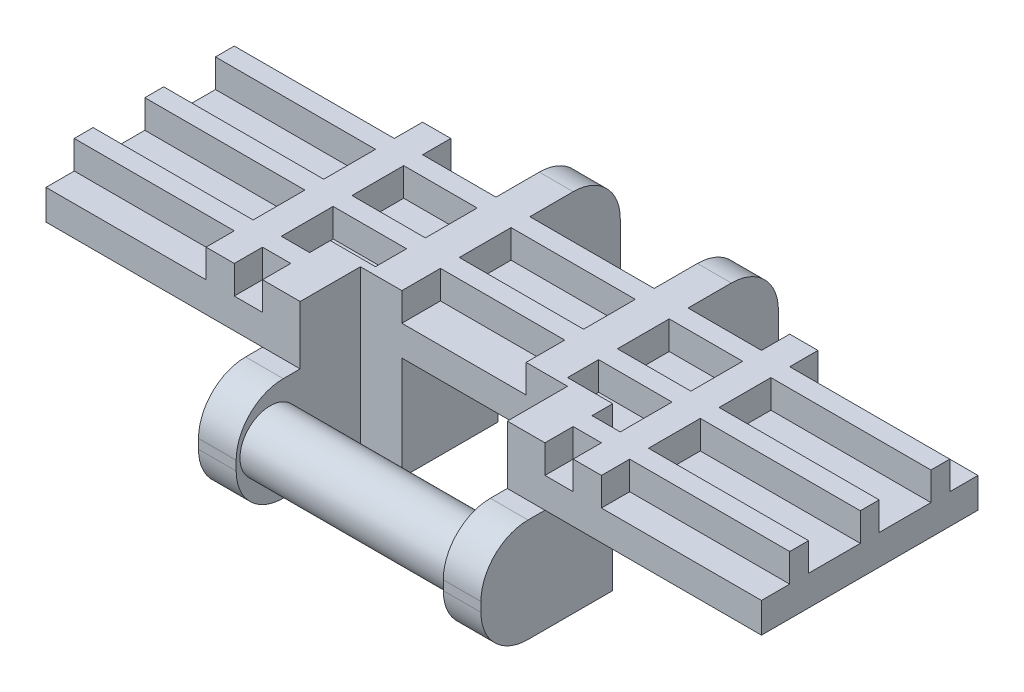
SolidWorks part; units mm, degrees
ref_plane "前视基准面" through (0, 0, 0) normal (0, 0, 1) x (1, 0, 0)
ref_plane "上视基准面" through (0, 0, 0) normal (0, 1, 0) x (1, 0, 0)
ref_plane "右视基准面" through (0, 0, 0) normal (1, 0, 0) x (0, 0, -1)
other "Configuration Table"
sketch "草图1" plane through (0, 0, 0) normal (0, 1, 0) x (1, 0, 0)
  line L1 (-19, -5.75) -> (19, -5.75)
  line L2 (-19, -5.75) -> (-19, 5.75)
  line L3 (-19, 5.75) -> (19, 5.75)
  line L4 (19, -5.75) -> (19, 5.75)
  line L5 (-19, -5.75) -> (19, 5.75) construction
  line L6 (-19, 5.75) -> (19, -5.75) construction
  line L13 (-19, 4.25) -> (19, 4.25)
  line L14 (-19, 4.25) -> (-19, 3.25)
  line L15 (-19, 3.25) -> (19, 3.25)
  line L16 (19, 4.25) -> (19, 3.25)
  line L17 (-19, 0.5) -> (19, 0.5)
  line L18 (-19, 0.5) -> (-19, -0.5)
  line L19 (-19, -0.5) -> (19, -0.5)
  line L20 (19, 0.5) -> (19, -0.5)
  line L21 (-19, -3.25) -> (19, -3.25)
  line L22 (-19, -3.25) -> (-19, -4.25)
  line L23 (-19, -4.25) -> (19, -4.25)
  line L24 (19, -3.25) -> (19, -4.25)
  line L25 (-10.5, 5.75) -> (-9, 5.75)
  line L26 (-10.5, 5.75) -> (-10.5, -5.75)
  line L27 (-10.5, -5.75) -> (-9, -5.75)
  line L28 (-9, 5.75) -> (-9, -5.75)
  line L29 (10.5, 5.75) -> (9, 5.75)
  line L30 (10.5, 5.75) -> (10.5, -5.75)
  line L31 (10.5, -5.75) -> (9, -5.75)
  line L32 (9, 5.75) -> (9, -5.75)
  point P0 (0, 0)
  point P6 (0, 0)
  dimension "D1" = 38
  dimension "D2" = 11.5
  dimension "D3" = 9
  dimension "D4" = 9
  dimension "D5" = 1
  dimension "D6" = 1.5
  dimension "D7" = 1.5
  dimension "D8" = 5.25
  dimension "D9" = 1.5
extrude "凸台-拉伸1" add sketch "草图1" along normal blind 1.6 contours L2 L3 L4 L1
extrude "凸台-拉伸2" add sketch "草图1<3>" along normal blind 1.5 from surface contours L13 L16 L15 L14 | L17 L20 L19 L18 | L21 L24 L23 L22 | L26 L27 L28 L25 | L30 L31 L32 L29 starting at face at (0, 1.6, 0)
sketch "草图1<3>" plane through (0, 0, 0) normal (0, 1, 0) x (1, 0, 0) same geometry as "草图1"
sketch "草图2" plane through (0, 0, 0) normal (0, 1, 0) x (1, 0, 0)
  line L0 (0, 0) -> (0, -13.8005) construction
  line L1 (-5.1, 9.05) -> (5.1, 9.05)
  line L2 (-5.1, 9.05) -> (-5.1, -2.55)
  line L3 (-5.1, -2.55) -> (5.1, -2.55)
  line L4 (5.1, 9.05) -> (5.1, -2.55)
  line L5 (-7.5, -2.55) -> (7.5, -2.55)
  line L8 (-3.3, 9.05) -> (3.3, 9.05)
  line L9 (-3.3, 9.05) -> (-3.3, -2.55)
  line L10 (-3.3, -2.55) -> (3.3, -2.55)
  line L11 (3.3, 9.05) -> (3.3, -2.55)
  line L16 (-9, -5.75) -> (9, -5.75) construction
  line L17 (-9, 5.75) -> (9, 5.75) construction
  line L18 (-5.5, -2.15) -> (-5.5, -9.15)
  line L19 (-7.5, -2.15) -> (7.5, -2.15)
  line L20 (-7.5, -2.15) -> (-7.5, -9.15)
  line L21 (-7.5, -9.15) -> (7.5, -9.15)
  line L22 (7.5, -2.15) -> (7.5, -9.15)
  line L23 (5.5, -2.15) -> (5.5, -9.15)
  point P5 (0, -2.55)
  point P15 (0, 9.05)
  point P20 (0, -9.15)
  point P28 (7.5, -2.55)
  dimension "D1" = 10.2
  dimension "D2" = 3.2
  dimension "D3" = 6.6
  dimension "D4" = 3.3
  dimension "D5" = 15
  dimension "D6" = 2
  dimension "D7" = 2
  dimension "D8" = 3.4
  dimension "D9" = 7
extrude "凸台-拉伸3" add sketch "草图2" against normal blind 8.6 from surface contours L1 L11 L3 L4 | L9 L1 L2 L3 | L20 L21 L18 L19 | L19 L23 L21 L22 | L19 L18 L5 L2 | L19 L20 L5 L18 | L19 L2 L3 L9 | L19 L11 L3 L4 | L23 L19 L4 L5 | L19 L23 L5 L22 region at (-4.2, 0, -3.45) region at (-4.2, 0, 2.35) region at (-5.3, 0, 2.35) region at (4.2, 0, -3.45) region at (-6.5, 0, 2.35) region at (4.2, 0, 2.35) region at (-6.5, 0, 5.85) region at (5.3, 0, 2.35) region at (6.5, 0, 2.35) region at (6.5, 0, 5.85) starting at face at (0, 3.1, 0)
extrude "切除-拉伸1" cut sketch "草图2<3>" along normal through all contours L0 L5 L3 L18 L21 | L10 L0 L21 L23 L5 L3 region at (2.75, 0, 5.85) region at (-2.75, 0, 5.85)
sketch "草图2<3>" plane through (0, 0, 0) normal (0, 1, 0) x (1, 0, 0) same geometry as "草图2"
fillet "圆角1" radius 3 2 edges at (-5.1, -2.75, 2.15) (5.1, -2.75, 2.15)
sketch "草图3" plane through (-5.5, 0, 0) normal (1, 0, 0) x (0, 0, -1)
  line L0 (-5.75, 1.6) -> (-5.75, 0) construction
  line L1 (5.75, 1.6) -> (5.75, 0) construction
  line L3 (2.55, -3.75) -> (9.05, -3.75)
  line L4 (2.55, -3.75) -> (2.55, -5.5)
  line L5 (2.55, -5.5) -> (9.05, -5.5)
  line L6 (9.05, -3.75) -> (9.05, -5.5)
  line L7 (-9.15, -5.5) -> (-9.15, 3.1) construction
  line L8 (-5.75, 3.1) -> (-9.15, 3.1)
  line L9 (-5.75, 3.1) -> (-5.75, 0)
  line L10 (-5.75, 0) -> (-9.15, 0)
  line L11 (-9.15, 3.1) -> (-9.15, 0)
  circle A0 centre (-7.35, -2.5) radius 1.6
  circle A1 centre (5.75, -2.5) radius 1.7
  dimension "D1" = 3.2
  dimension "D3" = 3.4
  dimension "D2" = 2.5
  dimension "D4" = 1.75
  dimension "D5" = 6.5
extrude "凸台-拉伸4" add sketch "草图3" along normal up to next contours A0
extrude "切除-拉伸2" cut sketch "草图3<3>" along normal through all both and the other way through all contours L3 L6 L5 L4 | A1 | L11 L10 L9 L8
sketch "草图3<3>" plane through (-5.5, 0, 0) normal (1, 0, 0) x (0, 0, -1) same geometry as "草图3"
fillet "圆角2" radius 2.5 4 edges at (6.5, -5.5, 9.15) (-6.5, -5.5, 9.15) (-6.5, 0, 9.15) (6.5, 0, 9.15)
fillet "圆角3" radius 2.5 2 edges at (-4.2, 3.1, -9.05) (4.2, 3.1, -9.05)
fillet "圆角4" radius 1 2 edges at (-4.2, -3.75, -9.05) (4.2, -3.75, -9.05)
fillet "圆角5" radius 0.5 4 edges at (-4.2, -3.75, -6.9022) (4.2, -3.75, -6.9022) (4.2, -3.75, -4.5978) (-4.2, -3.75, -4.5978)
